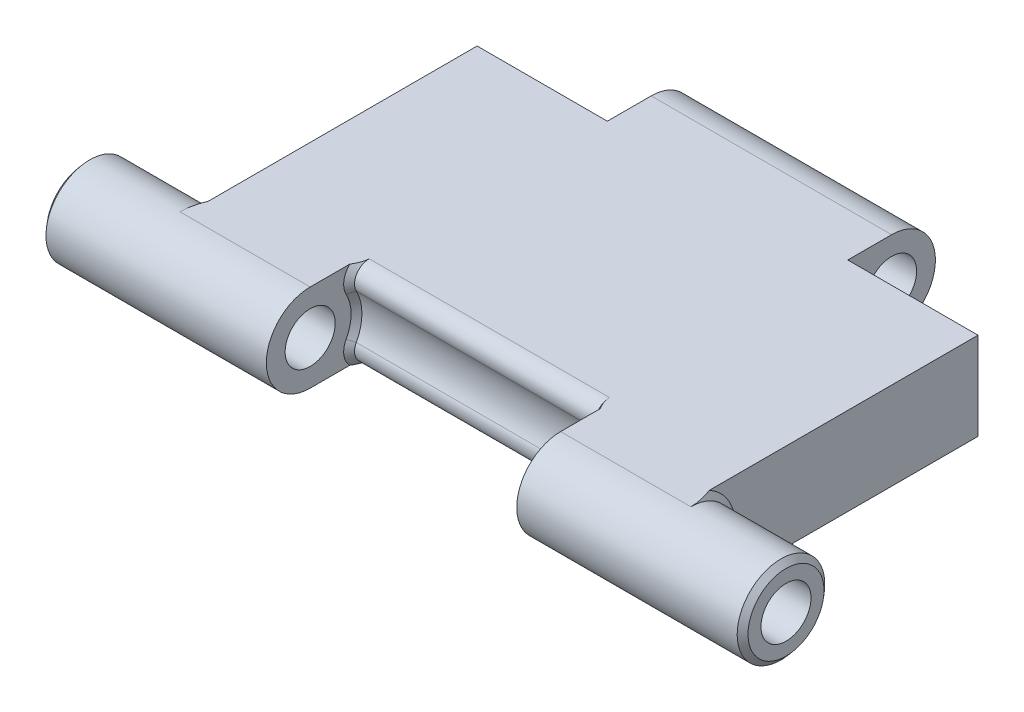
SolidWorks part; units mm, degrees
other "Markup1"
sketch "Sketch10" plane through (-10.5, 2.0625, -6.5697) normal (-0.116, 0.9645, -0.2372) x (-0.6238, 0.1151, 0.7731)
ref_plane "Front Plane" through (0, 0, 0) normal (0, 0, 1) x (1, 0, 0)
ref_plane "Top Plane" through (0, 0, 0) normal (0, 1, 0) x (1, 0, 0)
ref_plane "Right Plane" through (0, 0, 0) normal (1, 0, 0) x (0, 0, -1)
sketch "Sketch1" plane through (0, 0, 0) normal (0, 1, 0) x (1, 0, 0)
  line L1 (-5, 2.5) -> (5, 2.5)
  line L2 (-5, 2.5) -> (-5, -2.5)
  line L3 (-5, -2.5) -> (5, -2.5)
  line L4 (5, 2.5) -> (5, -2.5)
  line L5 (-5, 2.5) -> (5, -2.5) construction
  line L6 (-5, -2.5) -> (5, 2.5) construction
  point P0 (0, 0)
extrude "Boss-Extrude1" add sketch "Sketch1" along normal blind 1.5
sketch "Sketch4" plane through (0, 0, 0) normal (1, 0, 0) x (0, 0, -1)
  line L0 (-2.5, 1.5) -> (-2.5, 0) construction
  circle A0 centre (-2.5, 0.75) radius 0.75
extrude "Boss-Extrude3" add sketch "Sketch4" along normal mid plane 14
sketch "Sketch5" plane through (0, 0, 0) normal (1, 0, 0) x (0, 0, -1)
  circle A2 centre (-2.5, 0.75) radius 0.8
  dimension "D1" = 1.6
extrude "Cut-Extrude1" cut sketch "Sketch5" against normal mid plane 5
fillet "Fillet1" radius 0.25 2 edges at (0, 1.5, 2.2216) (0, 0, 2.2216)
sketch "Sketch8" plane through (0, 0, 0) normal (1, 0, 0) x (0, 0, -1)
  line L12 (3.25, 1.5) -> (2.5, 1.5)
  line L13 (2.5, 1.5) -> (2.5, 0)
  line L14 (2.5, 0) -> (3.25, 0)
  arc A18 (3.25, 0) -> (3.25, 1.5) centre (3.25, 0.75) ccw
  circle A19 centre (3.25, 0.75) radius 0.25
  dimension "D1" = 0.5
extrude "Boss-Extrude5" add sketch "Sketch8" along normal mid plane 4.8
chamfer "Chamfer3" distance 0.1 angle 45 10 edges at (-2.5, 0.1221, 1.7915) (-2.5, 1.3779, 1.7915) (-2.5, 0.75, 1.7) (2.5, 0.1221, 1.7915) (2.5, 1.3779, 1.7915) (2.5, 0.75, 1.7) (-7, 0.75, 1.75) (7, 0.75, 1.75) (5, 0.75, 1.75) (-5, 0.75, 1.75)
scale "Scale1" scale about centroid uniform scaling no x scale factor 1.5 y scale factor 1.75 z scale factor 1.75
sketch "Sketch12" plane through (10.5, 0, 0) normal (1, 0, 0) x (0, 0, -1)
  circle A0 centre (-4.4532, 0.75) radius 0.75
  circle A1 centre (5.6093, 0.75) radius 0.75
extrude "Cut-Extrude2" cut sketch "Sketch12" against normal up to surface (21 mm away) up to face at (-10.5, -0.3875, 4.4532)
